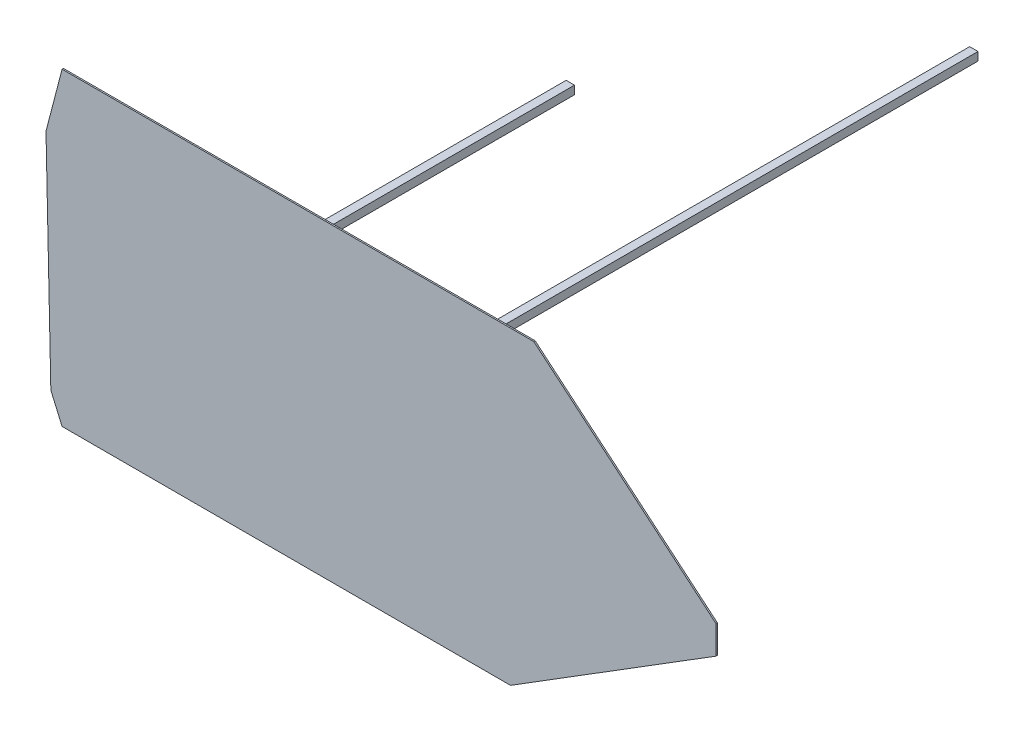
SolidWorks part; units mm, degrees
ref_plane "Front" through (0, 0, 0) normal (0, 0, 1) x (1, 0, 0)
ref_plane "Top" through (0, 0, 0) normal (0, 1, 0) x (1, 0, 0)
ref_plane "Right" through (0, 0, 0) normal (1, 0, 0) x (0, 0, -1)
sketch "Esquisse1" plane through (0, 0, 0) normal (0, 0, 1) x (1, 0, 0)
  line L1 (0, 0) -> (50, 0)
  line L2 (0, 0) -> (0, 50)
  line L3 (0, 50) -> (50, 50)
  line L4 (50, 0) -> (50, 50)
  dimension "D1" = 50
  dimension "D2" = 50
extrude "Boss.-Extru.1" add sketch "Esquisse1" along normal blind 5
sketch "Esquisse2" plane through (0, 0, 5) normal (0, 0, 1) x (1, 0, 0)
  line L0 (-5.6535, 9.3332) -> (57.2852, 53.4636)
  line L1 (57.2852, 53.4636) -> (231.6916, 53.4636)
  line L2 (231.6916, 53.4636) -> (285.9358, -3.0527)
  line L3 (285.9358, -3.0527) -> (284, -82.5096)
  line L4 (284, -82.5096) -> (207.7062, -129.7611)
  line L5 (207.7062, -129.7611) -> (50.4315, -129.7611)
  line L6 (50.4315, -129.7611) -> (-5.6535, -85.3866)
  line L7 (-5.6535, -85.3866) -> (-5.6535, 9.3332)
  line L8 (261, -129.7611) -> (23, -129.7611) construction
  line L9 (284, 24.7389) -> (284, -104.2611) construction
extrude "Boss.-Extru.2" add sketch "Esquisse2" against normal up to vertex (5 mm away) up to point (0, 50, 0)
sketch "Esquisse3" plane through (0, 0, 0) normal (0, 0, -1) x (-1, 0, 0)
  line L0 (0, -121.7217) -> (6, -121.7217)
  line L1 (6, -121.7217) -> (6, -115.7217)
  line L2 (6, -115.7217) -> (0, -115.7217)
  line L4 (0, -115.7217) -> (0, -121.7217)
  line L6 (-284, 44.2389) -> (-290, 44.2389)
  line L7 (-284, 44.2389) -> (-284, 50.2389)
  line L8 (-284, 50.2389) -> (-290, 50.2389)
  line L9 (-290, 44.2389) -> (-290, 50.2389)
  dimension "D1" = 6
  dimension "D2" = 6
  dimension "D3" = 6
  dimension "D4" = 6
extrude "Boss.-Extru.3" add sketch "Esquisse3" along normal blind 350
sketch "Esquisse4" plane through (0, 0, 5) normal (0, 0, 1) x (1, 0, 0)
  line L0 (-12.2793, 66.0481) -> (326.7277, 66.0481)
  line L1 (326.7277, 66.0481) -> (457.7032, -44.0432)
  line L2 (457.7032, -44.0432) -> (457.7032, -64.2948)
  line L3 (457.7032, -64.2948) -> (309.9939, -156.3257)
  line L4 (309.9939, -156.3257) -> (-12.2793, -156.3257)
  line L5 (-12.2793, -156.3257) -> (-20.3705, -137.7747)
  line L6 (-20.3705, -137.7747) -> (-23.8479, 21.7019)
  line L7 (-23.8479, 21.7019) -> (-12.2793, 66.0481)
extrude "Boss.-Extru.4" add sketch "Esquisse4" along normal blind 1
